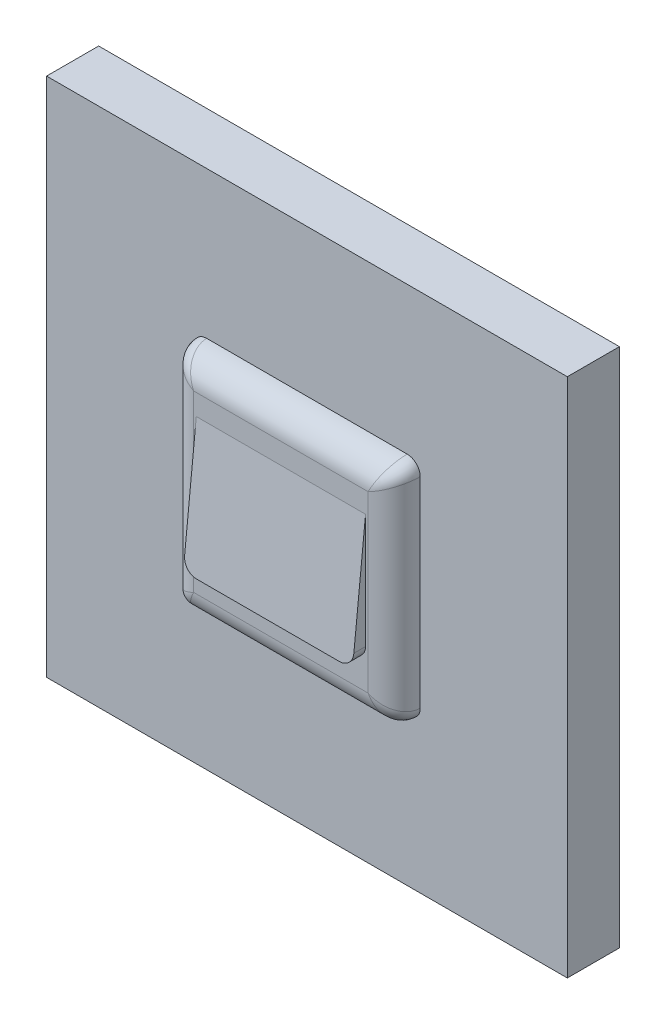
SolidWorks part; units mm, degrees
ref_plane "Front Plane" through (0, 0, 0) normal (0, 0, 1) x (1, 0, 0)
ref_plane "Top Plane" through (0, 0, 0) normal (0, 1, 0) x (1, 0, 0)
ref_plane "Right Plane" through (0, 0, 0) normal (1, 0, 0) x (0, 0, -1)
sketch "Sketch1" plane through (0, 0, 0) normal (0, 0, 1) x (1, 0, 0)
  line L1 (-100, 100) -> (100, 100)
  line L2 (-100, 100) -> (-100, -100)
  line L3 (-100, -100) -> (100, -100)
  line L4 (100, 100) -> (100, -100)
  line L5 (-100, 100) -> (100, -100) construction
  line L6 (-100, -100) -> (100, 100) construction
  line L15 (-43.5, 43.5) -> (43.5, -43.5) construction
  line L16 (-43.5, -43.5) -> (43.5, 43.5) construction
  point P0 (0, 0)
  point P6 (0, 0)
  point P11 (0, 0)
  point P12 (0, 0)
  dimension "D1" = 200
  dimension "D2" = 200
extrude "Boss-Extrude1" add sketch "Sketch1" along normal blind 20
sketch "Sketch2" plane through (0, 0, 20) normal (0, 0, 1) x (1, 0, 0)
  line L1 (-43.5, 43.5) -> (43.5, 43.5)
  line L2 (-43.5, 43.5) -> (-43.5, -43.5)
  line L3 (-43.5, -43.5) -> (43.5, -43.5)
  line L4 (43.5, 43.5) -> (43.5, -43.5)
  line L5 (-43.5, 43.5) -> (43.5, -43.5) construction
  line L6 (-43.5, -43.5) -> (43.5, 43.5) construction
  point P0 (0, 0)
  dimension "D1" = 87
  dimension "D2" = 87
extrude "Boss-Extrude2" add sketch "Sketch2" along normal blind 10
sketch "Sketch3" plane through (0, 0, 30) normal (0, 0, 1) x (1, 0, 0)
  line L5 (0, 43.5) -> (0, -43.5)
  line L6 (43.5, 43.5) -> (-43.5, 43.5) construction
  line L10 (-43.5, -43.5) -> (43.5, -43.5) construction
  line L11 (-43.5, 43.5) -> (-43.5, -43.5) construction
  line L12 (-32.5, 25.5) -> (32.5, 25.5)
  line L13 (-32.5, 25.5) -> (-32.5, -23.5)
  line L14 (-32.5, -23.5) -> (32.5, -23.5)
  line L15 (32.5, 25.5) -> (32.5, -23.5)
  point P0 (0, 0)
  dimension "D1" = 49
  dimension "D2" = 65
  dimension "D3" = 18
  dimension "D4" = 11
  dimension "D5" = 20
extrude "Boss-Extrude3" add sketch "Sketch3" along normal blind 5 contours L15 L12 L5 L14 | L13 L14 L5 L12 | L13 L12 L15 L14 region at (16.25, 1, 30) region at (-16.25, 1, 30)
sketch "Sketch5" plane through (-32.5, 0, 0) normal (-1, 0, 0) x (0, 0, 1)
  line L0 (30, 25.5) -> (35, -23.5)
  line L1 (35, -23.5) -> (35, 25.5)
  line L2 (35, 25.5) -> (30, 25.5)
extrude "Cut-Extrude2" cut sketch "Sketch5" against normal blind 65
fillet "Fillet1" radius 5 4 edges at (-43.5, -43.5, 25) (43.5, -43.5, 25) (43.5, 43.5, 25) (-43.5, 43.5, 25)
fillet "Fillet8" radius 10 8 edges at (42.0355, 42.0355, 30) (43.5, 0, 30) (42.0355, -42.0355, 30) (0, -43.5, 30) (-42.0355, -42.0355, 30) (-43.5, 0, 30) (-42.0355, 42.0355, 30) (0, 43.5, 30)
fillet "Fillet9" radius 5 2 edges at (-32.5, -23.5, 32.5) (32.5, -23.5, 32.5)
